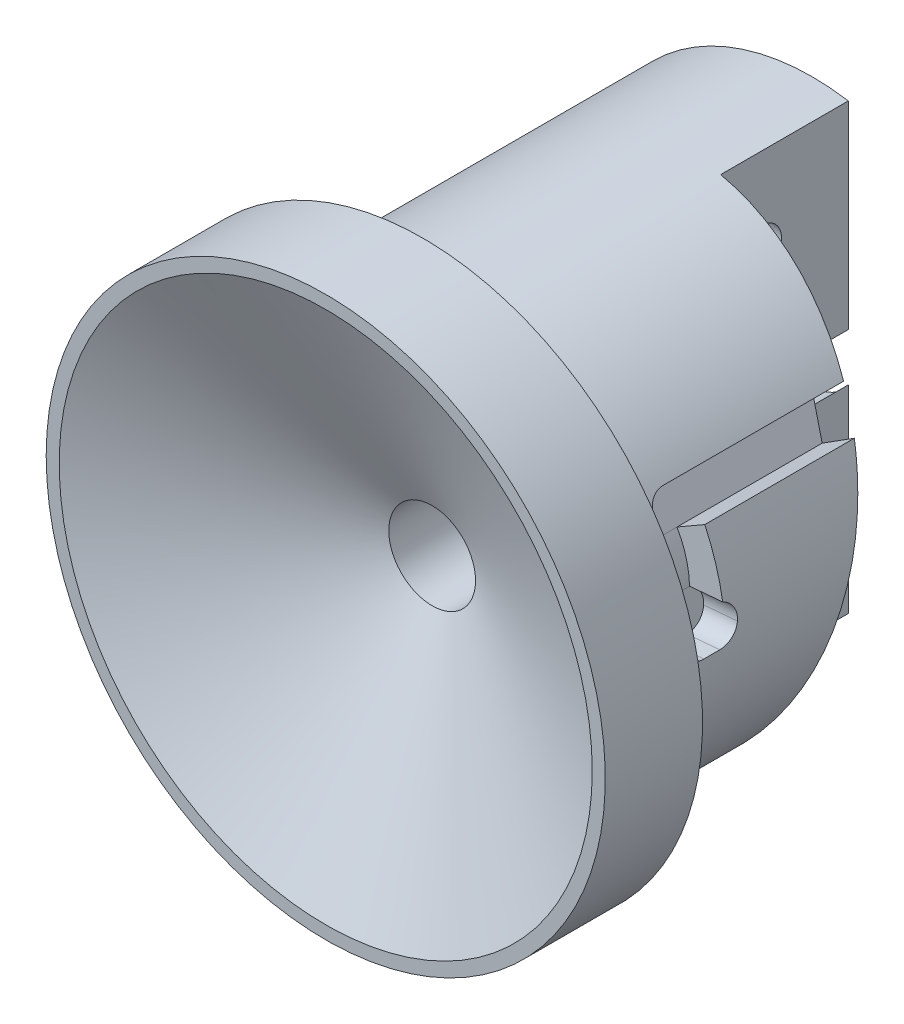
SolidWorks part; units mm, degrees
material "A-2 Steel"
ref_plane "Alzado" through (0, 0, 0) normal (0, 0, 1) x (1, 0, 0)
ref_plane "Planta" through (0, 0, 0) normal (0, 1, 0) x (1, 0, 0)
ref_plane "Vista lateral" through (0, 0, 0) normal (1, 0, 0) x (0, 0, -1)
sketch "Croquis2" plane through (0, 0, 0) normal (1, 0, 0) x (0, 0, -1)
  line L0 (0.3255, 0) -> (-7.0214, 0) construction
  line L1 (0, 2.8321) -> (31.75, 2.8321)
  line L2 (31.75, 2.8321) -> (31.75, 14.6812)
  line L3 (31.75, 14.6812) -> (6.35, 14.6812)
  line L4 (6.35, 14.6812) -> (6.35, 18.2499)
  line L5 (6.35, 18.2499) -> (0, 18.2499)
  line L6 (0, 18.2499) -> (0, 2.8321)
  dimension "D1" = 5.6642
  dimension "D2" = 36.4998
  dimension "D3" = 31.75
  dimension "D4" = 25.4
  dimension "D5" = 29.3624
revolve "Revolución1" add sketch "Croquis2" angle 360 about L0
sketch "Croquis3" plane through (0, 0, 0) normal (0, 1, 0) x (1, 0, 0)
  line L0 (0, 8.2982) -> (-17.399, 0)
  line L2 (-18.2499, 0) -> (18.2499, 0) construction
  line L3 (-17.399, 0) -> (0, 0)
  line L4 (0, 0) -> (0, 8.2982)
  line L5 (0, 0) -> (0, -3.613) construction
  dimension "D1" = 3.613
  dimension "D2" = 34.798
  dimension "D3" = 8.2982
revolve "Cortar-Revolución1" cut sketch "Croquis3" angle 360 about L5
sketch "Croquis4" plane through (0, 0, -31.75) normal (0, 0, -1) x (-1, 0, 0)
  line L0 (-2.3622, -14.4899) -> (-2.3622, 14.4899)
  circle A1 centre (0, 0) radius 14.6812 construction
  circle A3 centre (0, 0) radius 14.6812
  arc A4 (-2.3622, 14.4899) -> (-2.3622, -14.4899) centre (0, 0) ccw
  dimension "D1" = 2.3622
  dimension "D2" = 0
ref_plane "Plano1" through (2.3622, 0, 0) normal (-1, 0, 0) x (0, 1, 0)
sketch "Croquis5" plane through (2.3622, 0, 0) normal (-1, 0, 0) x (0, 1, 0)
  line L0 (14.4899, 23.4188) -> (-14.4899, 15.6537)
  line L1 (14.4899, 31.75) -> (-14.4899, 31.75) construction
  line L4 (-14.4899, 31.75) -> (-14.4899, 15.6537)
  line L6 (14.4899, 23.4188) -> (14.4899, 31.75)
  line L7 (-14.4899, 31.75) -> (14.4899, 31.75) construction
  line L8 (14.4899, 31.75) -> (-14.4899, 31.75)
  dimension "D1" = 15
  dimension "D2" = 8.3312
extrude "Cortar-Extruir1" cut sketch "Croquis5" against normal through all
hole_wizard "Taladro roscado #6-321" positions "Croquis6" profile "Croquis7" tap size "#6-32" standard "Ansi Inch"
sketch "Croquis6" plane through (2.3622, 0, 0) normal (1, 0, 0) x (0, 0, -1)
  line L0 (26.0341, 8.9408) -> (31.75, 8.9408) construction
  line L1 (31.75, -14.4899) -> (31.75, 14.4899) construction
  line L3 (0, 0) -> (31.75, 0) construction
  line L5 (19.9549, 1.5623) -> (23.4188, 14.4899) construction
  point P0 (26.0341, 8.9408)
  dimension "D1" = 8.9408
  dimension "D2" = 3.9624
sketch "Croquis7" plane through (2.3622, 8.9408, -26.0341) normal (0, 1, 0) x (0, 0, -1)
  line L0 (0, 0) -> (0, 11.7855)
  line L1 (0, 11.7855) -> (1.3525, 10.9728)
  line L2 (1.3525, 10.9728) -> (1.3525, 0)
  line L5 (1.3525, 0) -> (0, 0)
  line L10 (0, 11.7855) -> (-1.3526, 10.9728) construction
  line L11 (0, -6.35) -> (0, 107.95) construction
  dimension "Diámetro de perforador para roscar" = 2.7051
  dimension "Profundidad de perforador para roscar" = 10.9728
  dimension "Ángulo de perforador" = 118
cosmetic thread "Rosca de taladro1" parameters "D1"=7.0104, "D2"=3.5052
sketch "Croquis8" plane through (0, 0, -31.75) normal (0, 0, -1) x (-1, 0, 0)
  line L0 (-13.3178, 6.1786) -> (-11.4986, 5.1283)
  line L1 (-11.4986, 5.1283) -> (-10.1905, 7.3939)
  line L2 (-10.1905, 7.3939) -> (-12.0097, 8.4443)
  line L3 (0, 0) -> (-18.2499, 0) construction
  line L4 (0, 0) -> (-15.8049, 9.125) construction
  arc A0 (-2.3622, 14.4899) -> (-2.3622, -14.4899) centre (0, 0) ccw construction
  arc A1 (-12.0097, 8.4443) -> (-13.3178, 6.1786) centre (0, 0) ccw
  circle A2 centre (0, 0) radius 18.2499 construction
  point P12 (-10.8445, 6.2611)
  point P13 (-12.7143, 7.3406)
  dimension "D1" = 30
  dimension "D2" = 2.6162
  dimension "D3" = 2.159
extrude "Cortar-Extruir2" cut sketch "Croquis8" against normal offset from surface (22.9362 mm away) 2.4638 up to face at (-18.2499, 0, -6.35)
sketch "Croquis9" plane through (0, 0, -8.8138) normal (0, 0, -1) x (-1, 0, 0)
  line L0 (-10.8445, 6.2611) -> (0, 0) construction
  line L1 (-10.1905, 7.3939) -> (-11.4986, 5.1283) construction
  line L2 (0, 0) -> (-18.2499, 0) construction
  line L3 (0, 0) -> (-18.1805, 1.5906) construction
  line L5 (-12.3024, 2.3894) -> (-12.5304, -0.2168)
  line L6 (-12.5304, -0.2168) -> (-14.6812, -0.0287)
  line L7 (-11.0956, 5.8262) -> (-11.4986, 5.1283) construction
  line L8 (-11.0956, 5.8262) -> (-12.9579, 6.9014)
  circle A0 centre (0, 0) radius 18.2499 construction
  arc A1 (-13.3178, 6.1786) -> (-2.3622, -14.4899) centre (0, 0) ccw construction
  circle A2 centre (0, 0) radius 14.6812 construction
  arc A3 (-13.7662, 5.102) -> (-14.6812, -0.0287) centre (0, 0) ccw construction
  arc A4 (-11.0956, 5.8262) -> (-12.3024, 2.3894) centre (0, 0) ccw
  arc A5 (-12.9579, 6.9014) -> (-14.6812, -0.0287) centre (0, 0) ccw
  arc A6 (-12.0097, 8.4443) -> (-13.3178, 6.1786) centre (0, 0) ccw construction
  point P12 (-12.4164, 1.0863)
  point P15 (-14.4532, 2.5776)
  arc M11 (-12.0097, 8.4443) -> (-13.3178, 6.1786) centre (0, 0) ccw
  line M12 (-13.3178, 6.1786) -> (-11.4986, 5.1283)
  line M13 (-11.4986, 5.1283) -> (-10.1905, 7.3939)
  dimension "D1" = 25
  dimension "D2" = 2.6162
  dimension "D3" = 2.159
  dimension "D4" = 2.159
extrude "Cortar-Extruir3" cut sketch "Croquis9" along normal blind 2.6162 contours A5 L6 L5 A4 M12 M13 | L8 M13 M11 M12 region at (13.2214, 2.7992, -8.8138) region at (12.2183, 6.0109, -8.8138)
sketch "Croquis10" plane through (12.4164, 1.0863, 0) normal (0.9962, 0.0872, 0) x (0, 0, -1)
  line L0 (8.8138, 1.3081) -> (8.8138, -1.3081) construction
  line L1 (12.2428, -0.0974) -> (10.9347, -0.0974) construction
  line L3 (11.43, -1.3081) -> (11.43, 1.1133)
  arc A0 (11.43, -1.3081) -> (11.43, 1.1133) centre (10.9347, -0.0974) ccw
  dimension "D1" = 3.429
  dimension "D2" = 2.6162
extrude "Cortar-Extruir4" cut sketch "Croquis10" along normal through all
fillet "Redondeo1" radius 1.1938 2 edges at (11.1001, 7.9191, -8.8138) (13.6058, -0.1227, -8.8138)
sketch "Croquis11" plane through (0, 0, -11.43) normal (0, 0, 1) x (1, 0, 0)
  line L0 (10.1905, 7.3939) -> (11.4986, 5.1283) construction
  line L1 (11.0956, 5.8262) -> (11.4986, 5.1283)
  line L2 (12.5304, -0.2168) -> (12.3193, 2.1954) construction
  line L3 (12.3024, 2.3894) -> (12.3193, 2.1954)
  arc A0 (12.3193, 2.1954) -> (11.4986, 5.1283) centre (6.1834, 2.0595) ccw
  arc A10 (12.3024, 2.3894) -> (11.0956, 5.8262) centre (0, 0) ccw
  arc A11 (12.3024, 2.3894) -> (11.0956, 5.8262) centre (0, 0) ccw construction
extrude "Saliente-Extruir1" add sketch "Croquis11" along normal up to surface (2.6162 mm away) up to face at (12.3975, 4.0516, -8.8138)
fillet "Redondeo2" radius 1.1938 1 edges at (13.6058, -0.1227, -11.43)
